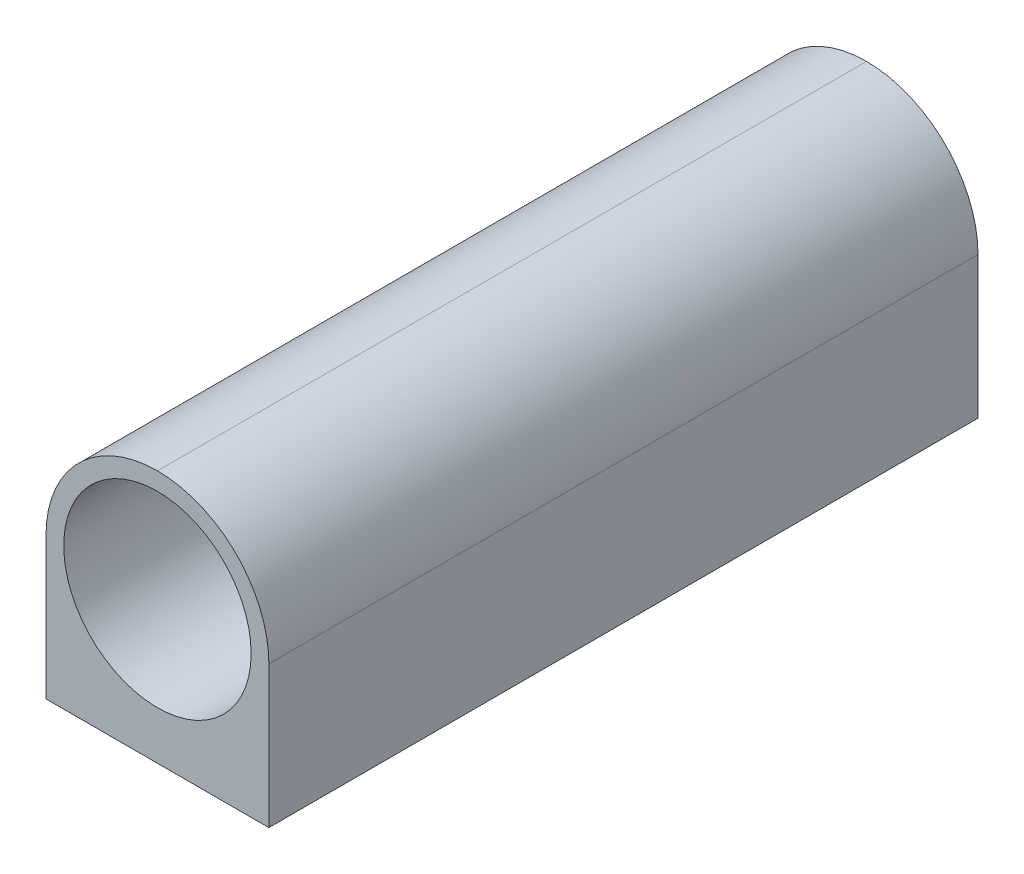
SolidWorks part; units mm, degrees
ref_plane "Alzado" through (0, 0, 0) normal (0, 0, 1) x (1, 0, 0)
ref_plane "Planta" through (0, 0, 0) normal (0, 1, 0) x (1, 0, 0)
ref_plane "Vista lateral" through (0, 0, 0) normal (1, 0, 0) x (0, 0, -1)
sketch "Croquis1" plane through (0, 0, 0) normal (0, 0, 1) x (1, 0, 0)
  line L0 (0, -11) -> (11, -11) construction
  line L1 (0, 0) -> (22, 0)
  line L2 (0, 0) -> (0, -22)
  line L3 (0, -22) -> (22, -22)
  line L4 (22, 0) -> (22, -22)
  line L5 (11, -11) -> (11, -22) construction
  circle A0 centre (11, -11) radius 9.25
  dimension "D3" = 18.5
  dimension "D1" = 22
  dimension "D2" = 22
extrude "Saliente-Extruir1" add sketch "Croquis1" along normal blind 70
fillet "Redondeo1" radius 11 2 edges at (22, 0, 35) (0, 0, 35)
sketch "Croquis2" plane through (0, -22, 0) normal (0, -1, 0) x (1, 0, 0)
  line L0 (11, 7.6221) -> (11, 0)
  line L1 (0, 0) -> (22, 0) construction
  line L2 (11, 7.6221) -> (11, 17.6221) construction
  line L3 (11, 17.6221) -> (11, 27.6221) construction
  circle A0 centre (11, 7.6221) radius 2.5
  circle A1 centre (11, 17.6221) radius 2.5
  circle A2 centre (11, 27.6221) radius 2.5
  dimension "D2" = 5
  dimension "D1" = 7.6221
  dimension "D3" = 10
sketch "Croquis6" plane through (0, -22, 0) normal (0, -1, 0) x (1, 0, 0)
  line L4 (0, 0) -> (22, 0)
  line L5 (22, 0) -> (22, 70)
  line L6 (22, 70) -> (0, 70)
  line L7 (0, 70) -> (0, 0)
  line L8 (0, 0) -> (22, 0)
  line L9 (22, 0) -> (22, 70)
  line L10 (22, 70) -> (0, 70)
  line L11 (0, 70) -> (0, 0)
  dimension "D1" = 0
extrude "Saliente-Extruir2" add sketch "Croquis6" along normal blind 3
sketch "Croquis9" plane through (0, -25, 0) normal (0, -1, 0) x (1, 0, 0)
  line L0 (11, 7.6221) -> (11, 0) construction
  line L1 (11, 7.6221) -> (11, 0)
  circle A1 centre (11, 27.6221) radius 2.5
  circle A2 centre (11, 27.6221) radius 2.5
  circle A3 centre (11, 17.6221) radius 2.5
  circle A4 centre (11, 17.6221) radius 2.5
  circle A5 centre (11, 7.6221) radius 2.5
  circle A6 centre (11, 7.6221) radius 2.5
  dimension "D1" = 0
  dimension "D2" = 0
  dimension "D3" = 0
hole_wizard "Taladro roscado M51" positions "Croquis10" profile "Croquis11" tap size "M5" standard "ISO"
sketch "Croquis10" plane through (0, -25, 0) normal (0, -1, 0) x (-1, 0, 0)
  point P0 (-11, -7.6221)
  point P3 (-11, -17.6221)
  point P6 (-11, -27.6221)
sketch "Croquis11" plane through (11, -25, 7.6221) normal (1, 0, 0) x (0, 0, -1)
  line L0 (0, 0) -> (0, 15.2618)
  line L1 (0, 15.2618) -> (2.1, 14)
  line L2 (2.1, 14) -> (2.1, 0)
  line L5 (2.1, 0) -> (0, 0)
  line L10 (0, 15.2618) -> (-2.1, 14) construction
  line L11 (0, -6.35) -> (0, 107.95) construction
  dimension "Diámetro de perforador para roscar" = 4.2
  dimension "Profundidad de perforador para roscar" = 14
  dimension "Ángulo de perforador" = 118
